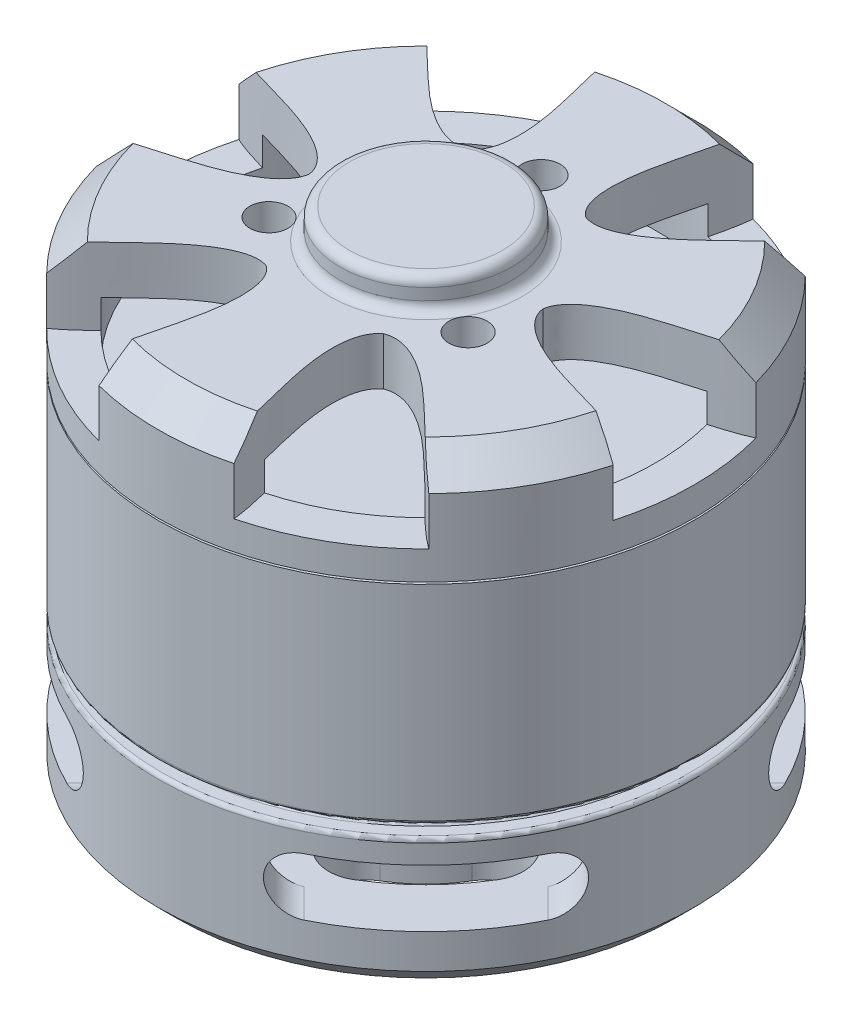
SolidWorks part; units mm, degrees
ref_plane "前视基准面" through (0, 0, 0) normal (0, 0, 1) x (1, 0, 0)
ref_plane "上视基准面" through (0, 0, 0) normal (0, 1, 0) x (1, 0, 0)
ref_plane "右视基准面" through (0, 0, 0) normal (1, 0, 0) x (0, 0, -1)
other "Configuration Table"
sketch "草图1" plane through (0, 0, 0) normal (0, 1, 0) x (1, 0, 0)
  line L0 (-12.8323, 0) -> (11.4175, 0) construction
  line L1 (0, 17.8689) -> (0, -21.1416) construction
  line L2 (0, 0) -> (-6.364, 6.364) construction
  circle A0 centre (0, 0) radius 14
  circle A1 centre (0, 8) radius 1.25
  circle A2 centre (9.5, 0) radius 1.25
  circle A3 centre (0, -8) radius 1.25
  circle A4 centre (-9.5, 0) radius 1.25
  arc A5 (-7.7145, 4.6353) -> (-4.6353, 7.7145) centre (0, 0) cw construction
  arc A6 (-5.6654, 9.4288) -> (-9.4288, 5.6654) centre (0, 0) ccw
  arc A7 (-3.6053, 6.0002) -> (-6.0002, 3.6053) centre (0, 0) ccw
  arc A8 (-3.6053, 6.0002) -> (-5.6654, 9.4288) centre (-4.6353, 7.7145) ccw
  arc A9 (-9.4288, 5.6654) -> (-6.0002, 3.6053) centre (-7.7145, 4.6353) ccw
  arc A10 (6.0002, 3.6053) -> (3.6053, 6.0002) centre (0, 0) ccw
  arc A11 (6.0002, 3.6053) -> (9.4288, 5.6654) centre (7.7145, 4.6353) ccw
  arc A12 (5.6654, 9.4288) -> (3.6053, 6.0002) centre (4.6353, 7.7145) ccw
  arc A13 (9.4288, 5.6654) -> (5.6654, 9.4288) centre (0, 0) ccw
  arc A14 (4.6353, 7.7145) -> (7.7145, 4.6353) centre (0, 0) cw construction
  arc A15 (3.6053, -6.0002) -> (6.0002, -3.6053) centre (0, 0) ccw
  arc A16 (3.6053, -6.0002) -> (5.6654, -9.4288) centre (4.6353, -7.7145) ccw
  arc A17 (9.4288, -5.6654) -> (6.0002, -3.6053) centre (7.7145, -4.6353) ccw
  arc A18 (5.6654, -9.4288) -> (9.4288, -5.6654) centre (0, 0) ccw
  arc A19 (7.7145, -4.6353) -> (4.6353, -7.7145) centre (0, 0) cw construction
  arc A20 (-6.0002, -3.6053) -> (-3.6053, -6.0002) centre (0, 0) ccw
  arc A21 (-6.0002, -3.6053) -> (-9.4288, -5.6654) centre (-7.7145, -4.6353) ccw
  arc A22 (-5.6654, -9.4288) -> (-3.6053, -6.0002) centre (-4.6353, -7.7145) ccw
  arc A23 (-9.4288, -5.6654) -> (-5.6654, -9.4288) centre (0, 0) ccw
  arc A24 (-4.6353, -7.7145) -> (-7.7145, -4.6353) centre (0, 0) cw construction
  point P17 (-6.364, 6.364)
  point P29 (6.364, 6.364)
  point P36 (6.364, -6.364)
  point P43 (-6.364, -6.364)
  point P48 (0, 0)
  dimension "D1" = 28
  dimension "D2" = 2.5
  dimension "D3" = 2.5
  dimension "D4" = 19
  dimension "D5" = 16
  dimension "D7" = 2
  dimension "D9" = 9
  dimension "D6" = 45
  dimension "D8" = 28
  dimension "D10" = 4
extrude "凸台-拉伸1" add sketch "草图1" along normal blind 7
chamfer "倒角2" distance 1 angle 45 1 edges at (0, 0, 14)
sketch "草图2" plane through (0, 7, 0) normal (0, 1, 0) x (1, 0, 0)
  circle A0 centre (0, 0) radius 13
  dimension "D1" = 26
extrude "凸台-拉伸2" add sketch "草图2" along normal blind 0.6
sketch "草图3" plane through (0, 7.6, 0) normal (0, 1, 0) x (1, 0, 0)
  circle A0 centre (0, 0) radius 14
extrude "凸台-拉伸3" add sketch "草图3" along normal blind 10.9
sketch "草图5" plane through (0, 18.5, 0) normal (0, 1, 0) x (1, 0, 0)
  circle A0 centre (0, 0) radius 13.5
  dimension "D1" = 27
extrude "凸台-拉伸4" add sketch "草图5" along normal blind 0.1
sketch "草图6" plane through (0, 18.6, 0) normal (0, 1, 0) x (1, 0, 0)
  circle A0 centre (0, 0) radius 14
  circle A1 centre (0, 0) radius 12
  dimension "D1" = 28
  dimension "D2" = 2
extrude "凸台-拉伸5" add sketch "草图6" along normal blind 3
sketch "草图8" plane through (0, 21.6, 0) normal (0, 1, 0) x (1, 0, 0)
  circle A0 centre (0, 0) radius 14
  dimension "D1" = 28
extrude "凸台-拉伸6" add sketch "草图8" along normal blind 2.5
chamfer "倒角1" distance 1.5 angle 45 1 edges at (0, 24.1, 14)
sketch "草图10" plane through (0, 24.1, 0) normal (0, 1, 0) x (1, 0, 0)
  line L0 (0, 14.745) -> (0, 0) construction
  line L1 (0, 0) -> (7.5472, 13.0721) construction
  line L2 (2.4873, 16.0942) -> (2.4873, 18.7746)
  line L3 (2.4873, 18.7746) -> (10.1474, 18.0073)
  line L4 (10.1474, 18.0073) -> (15.4804, 10.8347)
  line L5 (15.4804, 10.8347) -> (12.6943, 10.2011)
  line L7 (15.1816, 5.8931) -> (17.5029, 7.2333)
  line L8 (17.5029, 7.2333) -> (20.6685, 0.2158)
  line L9 (20.6685, 0.2158) -> (17.1233, -7.9891)
  line L10 (17.1233, -7.9891) -> (15.1816, -5.8931)
  line L11 (12.6943, -10.2011) -> (15.0156, -11.5413)
  line L12 (15.0156, -11.5413) -> (10.5211, -17.7915)
  line L13 (10.5211, -17.7915) -> (1.6429, -18.8237)
  line L14 (1.6429, -18.8237) -> (2.4873, -16.0942)
  line L15 (-2.4873, -16.0942) -> (-2.4873, -18.7746)
  line L16 (-2.4873, -18.7746) -> (-10.1474, -18.0073)
  line L17 (-10.1474, -18.0073) -> (-15.4804, -10.8347)
  line L18 (-15.4804, -10.8347) -> (-12.6943, -10.2011)
  line L19 (-15.1816, -5.8931) -> (-17.5029, -7.2333)
  line L20 (-17.5029, -7.2333) -> (-20.6685, -0.2158)
  line L21 (-20.6685, -0.2158) -> (-17.1233, 7.9891)
  line L22 (-17.1233, 7.9891) -> (-15.1816, 5.8931)
  line L23 (-12.6943, 10.2011) -> (-15.0156, 11.5413)
  line L24 (-15.0156, 11.5413) -> (-10.5211, 17.7915)
  line L25 (-10.5211, 17.7915) -> (-1.6429, 18.8237)
  line L26 (-1.6429, 18.8237) -> (-2.4873, 16.0942)
  spline S0 degree 3 poles (2.4873, 16.0942) (4.6567, 15.0736) (2.1032, 9.9112) (2.3365, 5.8216) (3.0482, 5.2796) knots 0 0 0 0 0.562936 0.825224 0.825224 0.825224 0.825224
  spline S1 degree 3 poles (12.6943, 10.2011) (10.7258, 11.5696) (7.5317, 6.7771) (3.8734, 4.9343) (3.0482, 5.2796) knots 0 0 0 0 0.562936 0.825224 0.825224 0.825224 0.825224
  spline S2 degree 3 poles (15.1816, -5.8931) (15.3825, -3.504) (9.635, -3.1341) (6.2099, -0.8873) (6.0963, 0) knots 0 0 0 0 0.562936 0.825224 0.825224 0.825224 0.825224
  spline S3 degree 3 poles (15.1816, 5.8931) (15.3825, 3.504) (9.635, 3.1341) (6.2099, 0.8873) (6.0963, 0) knots 0 0 0 0 0.562936 0.825224 0.825224 0.825224 0.825224
  spline S4 degree 3 poles (2.4873, -16.0942) (4.6567, -15.0736) (2.1032, -9.9112) (2.3365, -5.8216) (3.0482, -5.2796) knots 0 0 0 0 0.562936 0.825224 0.825224 0.825224 0.825224
  spline S5 degree 3 poles (12.6943, -10.2011) (10.7258, -11.5696) (7.5317, -6.7771) (3.8734, -4.9343) (3.0482, -5.2796) knots 0 0 0 0 0.562936 0.825224 0.825224 0.825224 0.825224
  spline S6 degree 3 poles (-12.6943, -10.2011) (-10.7258, -11.5696) (-7.5317, -6.7771) (-3.8734, -4.9343) (-3.0482, -5.2796) knots 0 0 0 0 0.562936 0.825224 0.825224 0.825224 0.825224
  spline S7 degree 3 poles (-2.4873, -16.0942) (-4.6567, -15.0736) (-2.1032, -9.9112) (-2.3365, -5.8216) (-3.0482, -5.2796) knots 0 0 0 0 0.562936 0.825224 0.825224 0.825224 0.825224
  spline S8 degree 3 poles (-15.1816, 5.8931) (-15.3825, 3.504) (-9.635, 3.1341) (-6.2099, 0.8873) (-6.0963, 0) knots 0 0 0 0 0.562936 0.825224 0.825224 0.825224 0.825224
  spline S9 degree 3 poles (-15.1816, -5.8931) (-15.3825, -3.504) (-9.635, -3.1341) (-6.2099, -0.8873) (-6.0963, 0) knots 0 0 0 0 0.562936 0.825224 0.825224 0.825224 0.825224
  spline S10 degree 3 poles (-2.4873, 16.0942) (-4.6567, 15.0736) (-2.1032, 9.9112) (-2.3365, 5.8216) (-3.0482, 5.2796) knots 0 0 0 0 0.562936 0.825224 0.825224 0.825224 0.825224
  spline S11 degree 3 poles (-12.6943, 10.2011) (-10.7258, 11.5696) (-7.5317, 6.7771) (-3.8734, 4.9343) (-3.0482, 5.2796) knots 0 0 0 0 0.562936 0.825224 0.825224 0.825224 0.825224
  point P52 (0, 0)
  point P66 (0, 0)
  dimension "D1" = 30
extrude "切除-拉伸2" cut sketch "草图10" against normal blind 4
sketch "草图11" plane through (0, 24.1, 0) normal (0, 1, 0) x (1, 0, 0)
  circle A0 centre (0, 0) radius 4.5
  dimension "D1" = 9
extrude "凸台-拉伸7" add sketch "草图11" along normal blind 1.6
fillet "圆角1" radius 0.5 2 edges at (0, 24.1, 4.5) (0, 25.7, 4.5)
fillet "圆角2" radius 0.2 4 edges at (0, 7.6, 14) (0, 7, 13) (0, 7.6, 13) (0, 7, 14)
sketch "草图12" plane through (0, 0, 0) normal (0, -1, 0) x (-1, 0, 0)
  circle A0 centre (0, 0) radius 3
  dimension "D1" = 6
extrude "凸台-拉伸8" add sketch "草图12" along normal blind 1.6
fillet "圆角3" radius 1 1 edges at (0, -1.6, -3)
sketch "草图13" plane through (0, 24.1, 0) normal (0, 1, 0) x (1, 0, 0)
  circle A0 centre (0, 6) radius 1
  circle A1 centre (5.1962, -3) radius 1
  circle A2 centre (-5.1962, -3) radius 1
  point P10 (0, 0)
  dimension "D1" = 6
  dimension "D2" = 2
extrude "切除-拉伸3" cut sketch "草图13" against normal up to next
ref_plane "基准面1" through (0, 0, 0) normal (-0.7071, 0, 0.7071) x (0.7071, 0, 0.7071)
sketch "草图14" plane through (0, 0, 0) normal (-0.7071, 0, 0.7071) x (0.7071, 0, 0.7071)
  line L0 (0, -3.1894) -> (0, 10.1312) construction
  line L1 (-4.5, 4.3) -> (4.5, 4.3) construction
  line L2 (-4.5, 5.8) -> (4.5, 5.8)
  line L3 (-4.5, 2.8) -> (4.5, 2.8)
  line L4 (-14, 6.8) -> (14, 6.8) construction
  arc A0 (-4.5, 5.8) -> (-4.5, 2.8) centre (-4.5, 4.3) ccw
  arc A1 (4.5, 2.8) -> (4.5, 5.8) centre (4.5, 4.3) ccw
  point P5 (0, 4.3)
  dimension "D2" = 1.5
  dimension "D1" = 1
  dimension "D3" = 9
extrude "切除-拉伸4" cut sketch "草图14" against normal mid plane 50
pattern_circular "阵列(圆周)1" count 2 every 90 about axis through (0, 0, 0) along (0, -1, 0) of "切除-拉伸4"
sketch "草图15" plane through (0, 2.8, 0) normal (0, 1, 0) x (1, 0, 0)
  circle A0 centre (0, 0) radius 12
extrude "切除-拉伸5" cut sketch "草图15" along normal up to surface (4.2 mm away) up to face at (-6.0984, 7, -6.0984)
